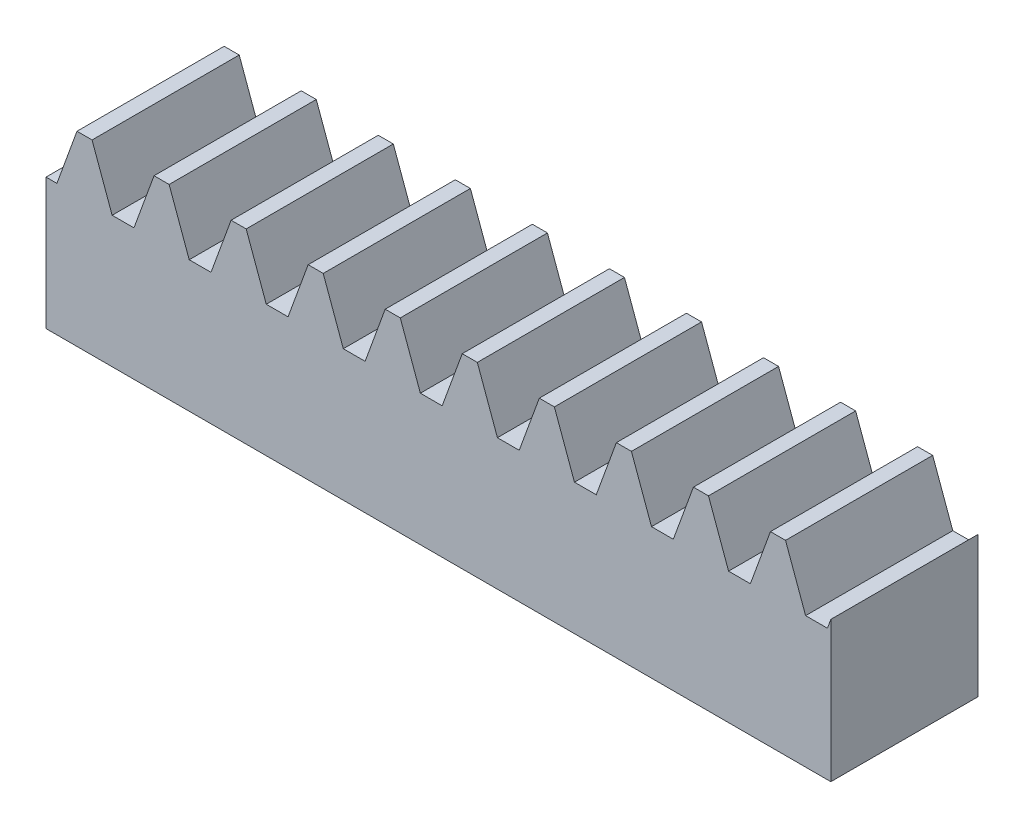
SolidWorks part; units mm, degrees
extrude "Blank" add sketch "BlankSke" against normal blind 3
sketch "BlankSke" plane through (0, 0, 0) normal (0, 0, 1) x (1, 0, 0)
  line L1 (0, 0) -> (16, 0)
  line L2 (0, 0) -> (0, 3.8)
  line L3 (0, 3.8) -> (16, 3.8)
  line L4 (16, 0) -> (16, 3.8)
  dimension "Length" = 16
ref_plane "Plane1" through (0, 0, 0) normal (0, 0, 1) x (1, 0, 0)
ref_plane "Plane2" through (0, 0, 0) normal (0, 1, 0) x (1, 0, 0)
ref_plane "Plane3" through (0, 0, 0) normal (1, 0, 0) x (0, 0, -1)
other "Configuration Table"
sketch "HoldingSke" plane through (0, 0, 0) normal (0, 1, 0) x (1, 0, 0)
  line L0 (0, 0) -> (0.2783, 1.9805)
  line L1 (-15, 0) -> (100, 0) construction
  line L2 (0, 0) -> (-2.1039, 2.3779)
  line L3 (0, 0) -> (-11.863, 4.5341)
  line L4 (0, 0) -> (8.4473, 1.7955)
  line L5 (0, 0) -> (-23.7986, -8.8762)
  line L6 (0, 0) -> (-10.5278, -7.1032)
  line L9 (-71.009, 38.7566) -> (-55.9739, 44.2289)
  line L10 (-76.2, 2.8779) -> (-72.4, 2.8779)
  line L11 (0, 0) -> (-3, 0)
  line L12 (-76.2, 101.6) -> (-76.181, 101.6)
  line L13 (24.9733, 27.94) -> (52.9518, 28.4284)
  line L14 (24.9733, 27.94) -> (24.9743, 27.94)
  line L15 (24.9733, 27.94) -> (100.4006, 29.5858)
  circle A0 centre (0, 0) radius 19.05
  circle A1 centre (0, 0) radius 1.9
  circle A2 centre (0, 0) radius 12.7
  dimension "Num_teeth" = 12
  dimension "Width" = 3
  dimension "Length" = 16
sketch "TooCutSkeIll" plane through (0, 0, 0) normal (0, 0, 1) x (1, 0, 0)
  line L0 (-0.4449, 3.7868) -> (-0.2524, 3.2579)
  line L1 (-0.134, 3.175) -> (0.134, 3.175)
  line L2 (0.2524, 3.2579) -> (0.4449, 3.7868)
  line L3 (16, 3.8) -> (0, 3.8) construction
  line L4 (0, 0) -> (0, 64.897) construction
  line L5 (-13.208, 3.8) -> (12.954, 3.8) construction
  line L6 (0, 0) -> (16, 0) construction
  line L7 (0.4497, 3.8) -> (0.4497, 48.7463) construction
  line L8 (-0.4497, 3.8) -> (-0.4497, 48.7463) construction
  line L9 (0.4637, 3.8) -> (0.4637, 4.3254)
  line L10 (-0.4637, 3.8) -> (-0.4637, 4.3254)
  line L11 (-0.4637, 4.3254) -> (0.4637, 4.3254)
  arc A0 (0.134, 3.175) -> (0.2524, 3.2579) centre (0.134, 3.301) ccw
  arc A1 (-0.2524, 3.2579) -> (-0.134, 3.175) centre (-0.134, 3.301) ccw
  arc A2 (0.4637, 3.8) -> (0.4449, 3.7868) centre (0.4637, 3.78) ccw
  arc A3 (-0.4449, 3.7868) -> (-0.4637, 3.8) centre (-0.4637, 3.78) ccw
  dimension "Addendum_plus" = 0.5254
  dimension "Pressure_angle" = 20
  dimension "Gap_width" = 0.8994
  dimension "Dedendum" = 0.625
extrude "ToothCutIll" [suppressed] cut sketch "TooCutSkeIll" against normal through all
sketch "TooCutSkeSim" plane through (0, 0, 0) normal (0, 0, 1) x (1, 0, 0)
  line L0 (0.2222, 2.675) -> (-0.2222, 2.675)
  line L1 (0.6409, 3.8254) -> (0.2222, 2.675)
  line L2 (0, 17.4625) -> (0, 53.467) construction
  line L3 (0.6409, 3.8254) -> (-0.6409, 3.8254)
  line L6 (-0.6409, 3.8254) -> (-0.2222, 2.675)
  line L9 (-0.4497, 3.3) -> (0.4497, 3.3) construction
  line L10 (0, 0) -> (16, 0) construction
  line L11 (0.4497, 3.3) -> (0.4497, 53.467) construction
  line L12 (-0.4497, 3.3) -> (-0.4497, 53.467) construction
  dimension "Addendum_plus" = 0.5254
  dimension "Pitch_height" = 3.3
  dimension "Pressure_angle" = 20
  dimension "Gap_width" = 0.8994
  dimension "Dedendum" = 0.625
extrude "ToothCutSim" cut sketch "TooCutSkeSim" against normal through all
pattern_linear "TeethCuts" count 12 spacing 1.5708 along (1, 0, 0) of "ToothCutIll", "ToothCutSim"
equation "' \"Module@HoldingSke\" = 6.35"
equation "' \"Num_teeth@HoldingSke\" = 12"
equation "' \"Ap@HoldingSke\" =  20"
equation "' \"Ap@HoldingSke\" = 20"
equation "' \"Width@HoldingSke\" = 0.25 * 25.4"
equation "' \"Show_teeth@HoldingSke\" = 500"
equation "' \"Backlash@HoldingSke\" = 0.009 * 25.4"
equation "' \"Addendum_fac@HoldingSke\" = 1.0"
equation "' \"Dedendum_fac@HoldingSke\" = 1.25"
equation "' \"Dedendum_add@HoldingSke\" = 0.00005 * 25.4"
equation "' \"Clearance_fac@HoldingSke\" = 0.25"
equation "' \"Pitch_height@HoldingSke\" = 1 * 25.4"
equation "' \"Length@HoldingSke\" = 4.71 * 25.4"
equation "\"Pitch@HoldingSke\" = 1 / \"Module@HoldingSke\""
equation "\"MPH@HoldingSke\" = \"Dedendum_fac@HoldingSke\" / \"Pitch@HoldingSke\" + 2 * \"Dedendum_add@HoldingSke\" + 0.002 * 25.4"
equation "\"MPH@HoldingSke\" = ((sgn( \"MPH@HoldingSke\" - \"Pitch_height@HoldingSke\")+1)*( \"MPH@HoldingSke\" - \"Pitch_height@HoldingSke\"))/2 + \"Pitch_height@HoldingSke\""
equation "\"Length@BlankSke\" =  \"Length@HoldingSke\""
equation "\"Face_width@Blank\" = \"Width@HoldingSke\""
equation "\"Pressure_angle@TooCutSkeIll\" = \"Ap@HoldingSke\""
equation "\"Addendum_plus@TooCutSkeIll\" =  \"Addendum_fac@HoldingSke\"  / \"Pitch@HoldingSke\" + 0.001 *25.4"
equation "\"Dedendum@TooCutSkeIll\" = \"Dedendum_fac@HoldingSke\"  / \"Pitch@HoldingSke\""
equation "\"Pitch_height@TooCutSkeIll\" =  \"MPH@HoldingSke\""
equation "\"Gap_width@TooCutSkeIll\" = 3.14159265 / 2 / \"Pitch@HoldingSke\" + 6 * \"Backlash@HoldingSke\""
equation "\"Pressure_angle@TooCutSkeSim\" = \"Ap@HoldingSke\""
equation "\"Addendum_plus@TooCutSkeSim\" =  \"Addendum_fac@HoldingSke\"  / \"Pitch@HoldingSke\" + 0.001 * 25.4"
equation "\"Dedendum@TooCutSkeSim\" = \"Dedendum_fac@HoldingSke\"  / \"Pitch@HoldingSke\""
equation "\"Gap_width@TooCutSkeSim\" = 3.14159265 / 2 / \"Pitch@HoldingSke\" + 6 * \"Backlash@HoldingSke\""
equation "\"Root_fillet@TooCutSkeIll\" = \"Clearance_fac@HoldingSke\" / \"Pitch@HoldingSke\" + \"Dedendum_add@HoldingSke\""
equation "\"Break_rad@TooCutSkeIll\" = 0.02 / \"Pitch@HoldingSke\" * 2"
equation "\"Linear_pitch@TeethCuts\" = 3.14159265 / \"Pitch@HoldingSke\""
equation "\"Num_teeth@HoldingSke\" = int( ( \"Length@HoldingSke\" + 0 ) / (3.14159265 / \"Pitch@HoldingSke\")) + 0.9999  + 1"
equation " \"Num_teeth@TeethCuts\" = int( \"Show_teeth@HoldingSke\" ) + 1"
equation " \"Num_teeth@TeethCuts\" = ((sgn( \"Num_teeth@TeethCuts\" - \"Num_teeth@HoldingSke\" )-1)*( \"Num_teeth@TeethCuts\" - \"Num_teeth@HoldingSke\" ))/-2+ \"Num_teeth@HoldingSke\""
equation " \"Num_teeth@TeethCuts\" = ((sgn( \"Num_teeth@TeethCuts\" - 2.0)+1)*( \"Num_teeth@TeethCuts\" - 2.0))/2 +2.0"
